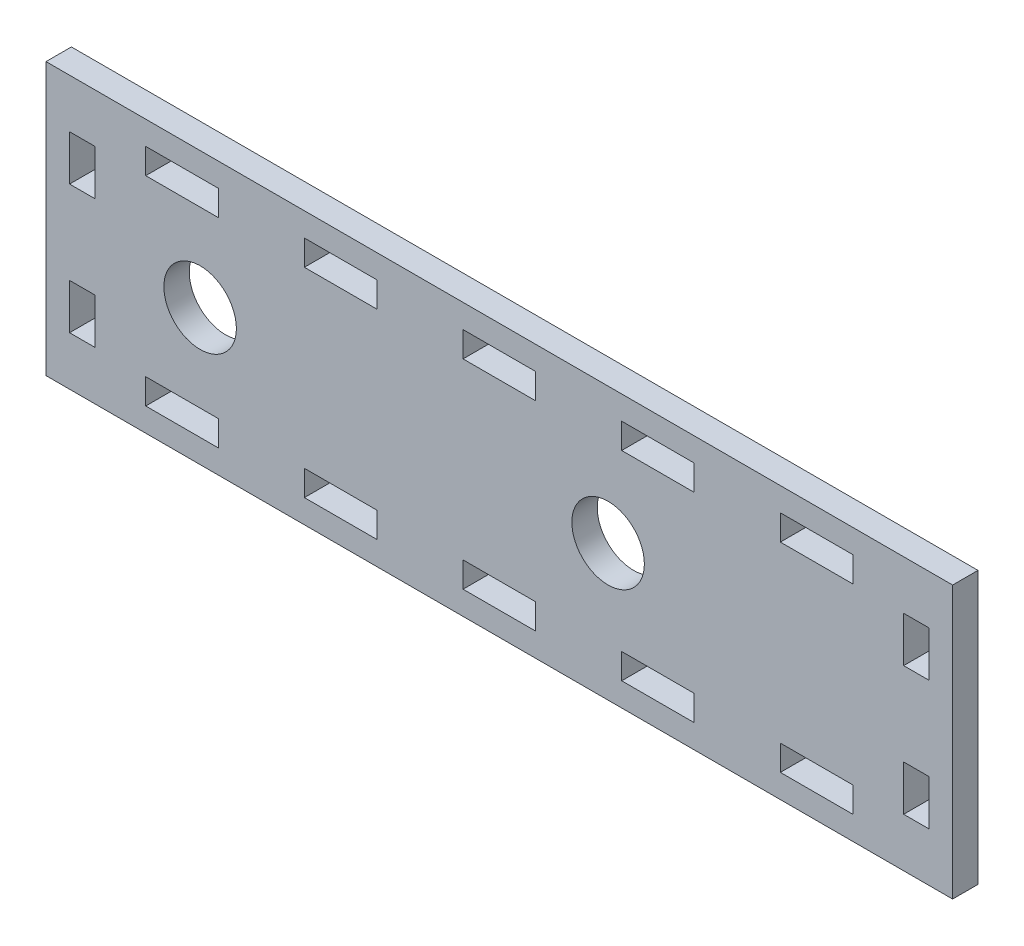
SolidWorks part; units mm, degrees
material "Фанера"
ref_plane "Front Plane" through (0, 0, 0) normal (0, 0, 1) x (1, 0, 0)
ref_plane "Top Plane" through (0, 0, 0) normal (0, 1, 0) x (1, 0, 0)
ref_plane "Right Plane" through (0, 0, 0) normal (1, 0, 0) x (0, 0, -1)
sketch "Эскиз1" plane through (0, 0, 0) normal (0, 0, 1) x (1, 0, 0)
  line L0 (-54.2706, 0) -> (97.4768, 0) construction
  line L1 (-50, -15) -> (50, -15)
  line L2 (-50, -15) -> (-50, 15)
  line L3 (-50, 15) -> (50, 15)
  line L4 (50, -15) -> (50, 15)
  line L5 (-50, -15) -> (50, 15) construction
  line L6 (-50, 15) -> (50, -15) construction
  line L7 (0, 34.2014) -> (0, -27.7796) construction
  line L8 (-56.037, 11) -> (-50, 11) construction
  line L9 (13.5, 12.4) -> (21.5, 12.4)
  line L10 (31, 9.6) -> (39, 9.6)
  line L11 (31, 9.6) -> (31, 12.4)
  line L12 (31, 12.4) -> (39, 12.4)
  line L13 (39, 9.6) -> (39, 12.4)
  line L14 (31, 9.6) -> (39, 12.4) construction
  line L15 (31, 12.4) -> (39, 9.6) construction
  line L16 (13.5, 9.6) -> (13.5, 12.4)
  line L17 (13.5, 9.6) -> (21.5, 9.6)
  line L18 (21.5, 9.6) -> (21.5, 12.4)
  line L19 (-4, 12.4) -> (4, 12.4)
  line L20 (-4, 9.6) -> (-4, 12.4)
  line L21 (-4, 9.6) -> (4, 9.6)
  line L22 (4, 9.6) -> (4, 12.4)
  line L23 (-21.5, 12.4) -> (-13.5, 12.4)
  line L24 (-21.5, 9.6) -> (-21.5, 12.4)
  line L25 (-21.5, 9.6) -> (-13.5, 9.6)
  line L26 (-13.5, 9.6) -> (-13.5, 12.4)
  line L27 (-39, 12.4) -> (-31, 12.4)
  line L28 (-39, 9.6) -> (-39, 12.4)
  line L29 (-39, 9.6) -> (-31, 9.6)
  line L30 (-31, 9.6) -> (-31, 12.4)
  line L31 (-13.5, -9.6) -> (-13.5, -12.4)
  line L32 (31, -12.4) -> (39, -12.4)
  line L33 (39, -9.6) -> (39, -12.4)
  line L34 (31, -9.6) -> (39, -9.6)
  line L35 (31, -9.6) -> (31, -12.4)
  line L36 (21.5, -9.6) -> (21.5, -12.4)
  line L37 (13.5, -9.6) -> (21.5, -9.6)
  line L38 (13.5, -9.6) -> (13.5, -12.4)
  line L39 (13.5, -12.4) -> (21.5, -12.4)
  line L40 (-4, -12.4) -> (4, -12.4)
  line L41 (4, -9.6) -> (4, -12.4)
  line L42 (-4, -9.6) -> (4, -9.6)
  line L43 (-4, -9.6) -> (-4, -12.4)
  line L44 (-21.5, -9.6) -> (-13.5, -9.6)
  line L45 (-21.5, -9.6) -> (-21.5, -12.4)
  line L46 (-21.5, -12.4) -> (-13.5, -12.4)
  line L47 (-39, -9.6) -> (-39, -12.4)
  line L48 (-39, -9.6) -> (-31, -9.6)
  line L49 (-31, -9.6) -> (-31, -12.4)
  line L50 (-39, -12.4) -> (-31, -12.4)
  line L51 (46, 24.6844) -> (46, 13.8) construction
  line L53 (44.6, -9.6) -> (47.4, -9.6)
  line L54 (44.6, -9.6) -> (44.6, -4.6)
  line L55 (44.6, -4.6) -> (47.4, -4.6)
  line L56 (47.4, -9.6) -> (47.4, -4.6)
  line L57 (44.6, -9.6) -> (47.4, -4.6) construction
  line L58 (44.6, -4.6) -> (47.4, -9.6) construction
  line L70 (-75.5, 40.993) -> (-75.5, -7.3926) construction
  line L71 (-44.6, 11) -> (63.2735, 11) construction
  line L72 (46, 0) -> (46, -21.7713) construction
  line L73 (44.6, 4.6) -> (47.4, 4.6)
  line L74 (47.4, 9.6) -> (47.4, 4.6)
  line L75 (44.6, 9.6) -> (47.4, 9.6)
  line L76 (44.6, 9.6) -> (44.6, 4.6)
  line L77 (-44.6, -4.6) -> (-47.4, -4.6)
  line L78 (-47.4, -9.6) -> (-47.4, -4.6)
  line L79 (-44.6, -9.6) -> (-47.4, -9.6)
  line L80 (-44.6, -9.6) -> (-44.6, -4.6)
  line L81 (-44.6, 9.6) -> (-44.6, 4.6)
  line L82 (-44.6, 9.6) -> (-47.4, 9.6)
  line L83 (-47.4, 9.6) -> (-47.4, 4.6)
  line L84 (-44.6, 4.6) -> (-47.4, 4.6)
  circle A0 centre (-33, 0) radius 4
  circle A1 centre (12, 0) radius 4
  circle A2 centre (-20.5, 0) radius 4
  circle A3 centre (33.5, 0) radius 4
  point P0 (0, 0)
  point P16 (35, 11)
  point P59 (46, -7.1)
  point P66 (46, -4.6518)
  dimension "D2" = 8
  dimension "D1" = 100
  dimension "D3" = 45
  dimension "D4" = 30
  dimension "D5" = 4
  dimension "D6" = 2.8
  dimension "D7" = 8
  dimension "D8" = 15
  dimension "D10" = 4
  dimension "D11" = 2.8
  dimension "D12" = 5
  dimension "D13" = 54
  dimension "D14" = 42.5
  dimension "D15" = 55
  dimension "D16" = 17
  dimension "D17" = 16.5
  dimension "D18" = 11.1
  dimension "D19" = 21.5
  dimension "D9" = 5
extrude "Бобышка-Вытянуть1" add sketch "Эскиз1" along normal mid plane 2.8 contours L1 L4 L3 L2 A3 A2 A1 A0 L73 L56 L53 L54 L55 L50 L47 L48 L49 L46 L45 L44 L31 L43 L42 L41 L40 L39 L38 L37 L36 L35 L34 L33 | A3 | A2 region at (0.1596, 0, 0) region at (-20.5, 0, 0) region at (33.5, 0, 0)
equation "\"D14@Эскиз1\"=170*0.25"
